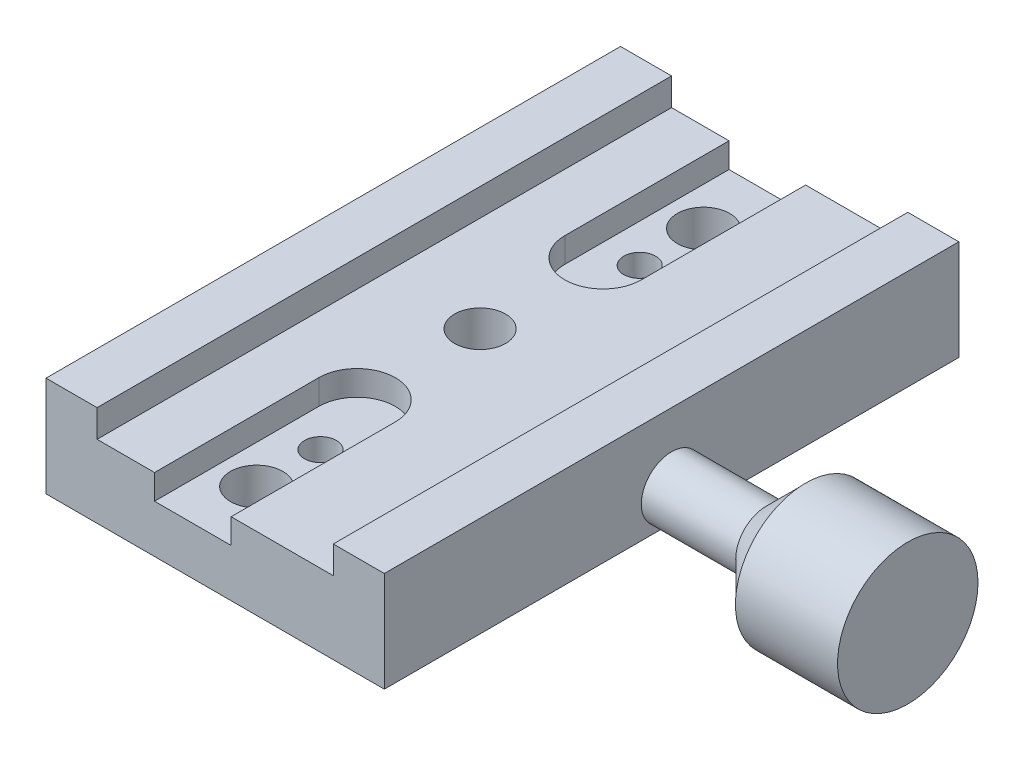
SolidWorks part; units mm, degrees
ref_plane "Front Plane" through (0, 0, 0) normal (0, 0, 1) x (1, 0, 0)
ref_plane "Top Plane" through (0, 0, 0) normal (0, 1, 0) x (1, 0, 0)
ref_plane "Right Plane" through (0, 0, 0) normal (1, 0, 0) x (0, 0, -1)
sketch "Sketch1" plane through (0, 0, 0) normal (0, 0, 1) x (1, 0, 0)
  line L0 (0, 0) -> (0, 27.4198) construction
  line L1 (0, 0) -> (30, 0)
  line L2 (30, 0) -> (30, 15.7)
  line L3 (30, 15.7) -> (22, 15.7)
  line L4 (22, 15.7) -> (22, 11.4)
  line L5 (22, 11.4) -> (0, 11.4)
  line L6 (0, 0) -> (-23, 0)
  line L7 (-23, 0) -> (-23, 15.7)
  line L8 (-23, 15.7) -> (-15, 15.7)
  line L9 (-15, 15.7) -> (-15, 11.4)
  line L10 (-15, 11.4) -> (0, 11.4)
  dimension "D1" = 30
  dimension "D2" = 15.7
  dimension "D3" = 8
  dimension "D4" = 11.4
  dimension "D5" = 53
  dimension "D6" = 8
extrude "Boss-Extrude1" add sketch "Sketch1" along normal blind 90
sketch "Sketch2" plane through (30, 0, 0) normal (1, 0, 0) x (0, 0, -1)
  line L0 (-45, 15.7) -> (-45, 0) construction
  line L1 (-90, 15.7) -> (0, 15.7) construction
  line L2 (-90, 0) -> (0, 0) construction
  circle A0 centre (-45, 4.9715) radius 4.75
  dimension "D1" = 9.5
extrude "Boss-Extrude2" add sketch "Sketch2" along normal offset from surface (37 mm away) 67 up to plane "Right Plane"
sketch "Sketch3" plane through (67, 0, 0) normal (1, 0, 0) x (0, 0, -1)
  circle A0 centre (-45, 4.9715) radius 11
  dimension "D1" = 22
extrude "Boss-Extrude3" add sketch "Sketch3" against normal blind 16
chamfer "Chamfer1" distance 6.2 angle 45 1 edges at (51, 4.9715, 40.25)
sketch "Sketch4" plane through (0, 0, 0) normal (0, 1, 0) x (1, 0, 0)
  line L0 (0, 0) -> (0, -90) construction
  line L1 (22, -90) -> (-15, -90) construction
  line L2 (0, -45) -> (-23, -45) construction
  line L3 (-23, -90) -> (-23, 0) construction
  circle A0 centre (0, -45) radius 4
  circle A1 centre (0, -20) radius 2.5
  circle A2 centre (0, -70) radius 2.5
  circle A3 centre (0, -10) radius 4.1
  circle A4 centre (0, -80) radius 4.1
  dimension "D1" = 8
  dimension "D2" = 50
  dimension "D3" = 5
  dimension "D4" = 8.2
  dimension "D5" = 70
extrude "Cut-Extrude1" cut sketch "Sketch4" along normal through all
sketch "Sketch5" plane through (0, 11.4, 0) normal (0, 1, 0) x (1, 0, 0)
  line L0 (0, -25.7294) -> (0, 7.9858) construction
  line L1 (-6, -25.7294) -> (-6, 7.9858)
  line L2 (6, -25.7294) -> (6, 7.9858)
  line L3 (0, -45) -> (12.6156, -45) construction
  line L4 (0, -64.2706) -> (0, -97.9858) construction
  line L5 (-6, -64.2706) -> (-6, -97.9858)
  line L6 (6, -64.2706) -> (6, -97.9858)
  arc A0 (-6, -25.7294) -> (6, -25.7294) centre (0, -25.7294) ccw
  arc A1 (6, 7.9858) -> (-6, 7.9858) centre (0, 7.9858) ccw
  arc A2 (-6, -64.2706) -> (6, -64.2706) centre (0, -64.2706) cw
  arc A3 (6, -97.9858) -> (-6, -97.9858) centre (0, -97.9858) cw
  point P3 (0, -8.8718)
  point P13 (0, -81.1282)
  dimension "D1" = 12
extrude "Cut-Extrude2" cut sketch "Sketch5" against normal offset from surface (3.9 mm away) 7.5 up to face at (0, 0, 75.9)
